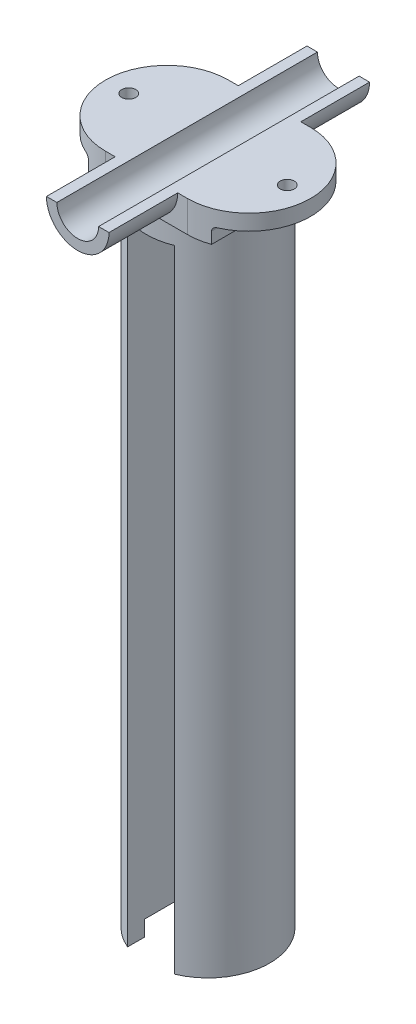
SolidWorks part; units mm, degrees
material "ABS"
ref_plane "Front Plane" through (0, 0, 0) normal (0, 0, 1) x (1, 0, 0)
ref_plane "Top Plane" through (0, 0, 0) normal (0, 1, 0) x (1, 0, 0)
ref_plane "Right Plane" through (0, 0, 0) normal (1, 0, 0) x (0, 0, -1)
sketch "Sketch1" plane through (0, 0, 0) normal (0, 1, 0) x (1, 0, 0)
  line L0 (-5.75, 13.8542) -> (-5.75, -13.8542)
  line L1 (5.75, 13.8542) -> (5.75, -13.8542)
  arc A0 (-5.75, 13.8542) -> (-5.75, -13.8542) centre (0, 0) ccw
  circle A1 centre (0, 0) radius 5 construction
  arc A2 (5.75, -13.8542) -> (5.75, 13.8542) centre (0, 0) ccw
  circle A3 centre (0, 0) radius 8
  circle A4 centre (-8, 0) radius 1.25
  circle A5 centre (8, 0) radius 1.25
  dimension "D1" = 30
  dimension "D4" = 10
  dimension "D5" = 16
  dimension "D6" = 2.5
  dimension "D7" = 2.5
  dimension "D2" = 5.75
  dimension "D3" = 5.75
extrude "Boss-Extrude1" add sketch "Sketch1" along normal blind 150 contours L0 A0 | A2 L1
sketch "Sketch2" plane through (0, 150, 0) normal (0, 1, 0) x (1, 0, 0)
  circle A0 centre (0, 0) radius 15
  arc A1 (5.75, -13.8542) -> (5.75, 13.8542) centre (0, 0) ccw construction
extrude "Boss-Extrude2" add sketch "Sketch2" along normal blind 5
sketch "Sketch3" plane through (0, 155, 0) normal (0, 1, 0) x (1, 0, 0)
  line L1 (-15, 31.75) -> (15, 31.75)
  line L2 (-15, 31.75) -> (-15, -31.75)
  line L3 (-15, -31.75) -> (15, -31.75)
  line L4 (15, 31.75) -> (15, -31.75)
  line L5 (-15, 31.75) -> (15, -31.75) construction
  line L6 (-15, -31.75) -> (15, 31.75) construction
  circle A0 centre (0, 0) radius 15 construction
  point P0 (0, 0)
  dimension "D1" = 63.5
extrude "Boss-Extrude3" add sketch "Sketch3" along normal blind 15.24
sketch "Sketch4" plane through (0, 0, 31.75) normal (0, 0, 1) x (1, 0, 0)
  line L0 (-15, 155) -> (15, 155) construction
  line L2 (-15, 170.24) -> (15, 170.24) construction
  circle A0 centre (0, 162.62) radius 5.08
  circle A1 centre (0, 162.62) radius 7.62
  point P7 (0, 170.24)
  line M1 (-15, 155) -> (15, 155)
  line M2 (15, 155) -> (15, 170.24)
  line M3 (15, 170.24) -> (-15, 170.24)
  line M4 (-15, 170.24) -> (-15, 155)
  dimension "D1" = 10.16
  dimension "D2" = 7.62
extrude "Cut-Extrude1" cut sketch "Sketch4" against normal through all contours A0
ref_plane "Plane1" through (0, 0, -15) normal (0, 0, -1) x (-1, 0, 0)
sketch "Sketch6" plane through (0, 0, -31.75) normal (0, 0, -1) x (-1, 0, 0)
  circle A0 centre (0, 162.62) radius 7.62
  line M2 (-15, 155) -> (15, 155)
  line M3 (15, 155) -> (15, 170.24)
  line M4 (15, 170.24) -> (-15, 170.24)
  line M5 (-15, 170.24) -> (-15, 155)
  dimension "D1" = 15.24
extrude "Cut-Extrude3" cut sketch "Sketch6" against normal up to surface (16.75 mm away) contours A0 M4 M5 M2 | A0 M2 M3 M4 region at (-10.3319, 162.62, -31.75) region at (10.3319, 162.62, -31.75) up to plane "Plane1"
ref_plane "Plane2" through (0, 0, 15) normal (0, 0, -1) x (-1, 0, 0)
extrude "Cut-Extrude4" cut sketch "Sketch4<4>" against normal up to surface (16.75 mm away) contours A1 M3 M4 M1 | A1 M1 M2 M3 region at (10.3319, 162.62, 31.75) region at (-10.3319, 162.62, 31.75) up to plane "Plane2"
sketch "Sketch4<4>" plane through (0, 0, 31.75) normal (0, 0, 1) x (1, 0, 0) same geometry as "Sketch4"
sketch "Sketch7" plane through (-15, 0, 0) normal (-1, 0, 0) x (0, 0, 1)
  line L0 (-31.75, 162.62) -> (31.75, 162.62)
  line L1 (-31.75, 170.24) -> (-31.75, 155) construction
  line L2 (31.75, 155) -> (31.75, 170.24) construction
  line L3 (31.75, 162.62) -> (31.75, 170.24)
  line L4 (31.75, 170.24) -> (-31.75, 170.24)
  line L5 (-31.75, 170.24) -> (-31.75, 162.62)
extrude "Cut-Extrude5" cut sketch "Sketch7" against normal through all
sketch "Sketch8" plane through (-15, 0, 0) normal (-1, 0, 0) x (0, 0, 1)
  line L0 (-15, 162.62) -> (15, 162.62) construction
  line L1 (-15, 162.62) -> (15, 162.62)
  line L2 (-15, 162.62) -> (-15, 158.81)
  line L3 (-15, 158.81) -> (15, 158.81)
  line L4 (15, 162.62) -> (15, 158.81)
  line L5 (-15, 162.62) -> (-15, 155) construction
  line L6 (15, 16.5) -> (15, -16.5) construction
  point P8 (-15, 158.81)
extrude "Boss-Extrude4" add sketch "Sketch8" along normal blind 10
mirror "Mirror2" about plane through (0, 0, 0) normal (1, 0, 0) of "Boss-Extrude4"
sketch "Sketch9" plane through (0, 162.62, 0) normal (0, 1, 0) x (1, 0, 0)
  line L0 (-7.62, 15) -> (-25, 15) construction
  line L1 (25, 15) -> (7.62, 15) construction
  line L2 (-16.31, 15) -> (-16.31, -15) construction
  line L3 (-7.62, -15) -> (-25, -15) construction
  line L4 (16.31, 15) -> (16.31, -15) construction
  line L5 (25, -15) -> (7.62, -15) construction
  circle A0 centre (-19.31, 0) radius 1.7
  circle A1 centre (19.31, 0) radius 1.7
  dimension "D1" = 3.4
  dimension "D2" = 3.4
  dimension "D3" = 3
  dimension "D4" = 3
sketch "Sketch10" plane through (0, 162.62, 0) normal (0, 1, 0) x (1, 0, 0)
  line L0 (16.5, 15) -> (-16.5, 15) construction
  line L1 (16.5, -15) -> (-16.5, -15) construction
  line L2 (25, 15) -> (7.62, 15) construction
  line L3 (25, -15) -> (25, 15) construction
  line L4 (25, -15) -> (7.62, -15) construction
  arc A0 (10, 15) -> (10, -15) centre (10, 0) cw
extrude "Cut-Extrude6" cut sketch "Sketch10" against normal through all and the other way through all
mirror "Mirror3" about plane through (0, 0, 0) normal (1, 0, 0) of "Cut-Extrude6"
extrude "Cut-Extrude7" cut sketch "Sketch1<4>" along normal blind 10 contours A5 | A4
sketch "Sketch1<4>" plane through (0, 0, 0) normal (0, 1, 0) x (1, 0, 0) same geometry as "Sketch1"
sketch "Sketch12" plane through (0, 0, 0) normal (0, -1, 0) x (1, 0, 0)
  line L0 (-5.75, 13.8542) -> (-5.75, 9.6695)
  line L1 (-5.75, -13.8542) -> (-5.75, 13.8542) construction
  line L2 (5.75, 13.8542) -> (5.75, 9.6695)
  line L3 (-5.75, -13.8542) -> (-5.75, -9.6695)
  line L4 (5.75, -9.6695) -> (5.75, -13.8542)
  line L5 (5.75, -13.8542) -> (5.75, 13.8542) construction
  line L6 (5.75, 13.8542) -> (5.75, -13.8542)
  line L7 (-5.75, 13.8542) -> (-5.75, -13.8542)
  circle A0 centre (0, 0) radius 11 construction
  circle A1 centre (0, 0) radius 11.25
  circle A2 centre (0, 0) radius 15
  circle A3 centre (8, 0) radius 1.25
  line M5 (-5.75, -13.8542) -> (-5.75, 13.8542)
  arc M6 (-5.75, 13.8542) -> (-5.75, -13.8542) centre (0, 0) ccw
  dimension "D1" = 22
  dimension "D2" = 22.5
  dimension "D3" = 30
extrude "Boss-Extrude5" add sketch "Sketch12" along normal blind 3.8 contours L4 A2 L2 A1 | A1 M5 M6 region at (-6.0421, 0, 11.7618) region at (12.232, 0, 8.167)
fillet "Fillet1" radius 1 2 edges at (15, 158.81, 0) (-15, 158.81, 0)
extrude "Cut-Extrude8" cut sketch "Sketch9" against normal up to next contours A0 | A1 region at (-19.31, 162.62, 0)
